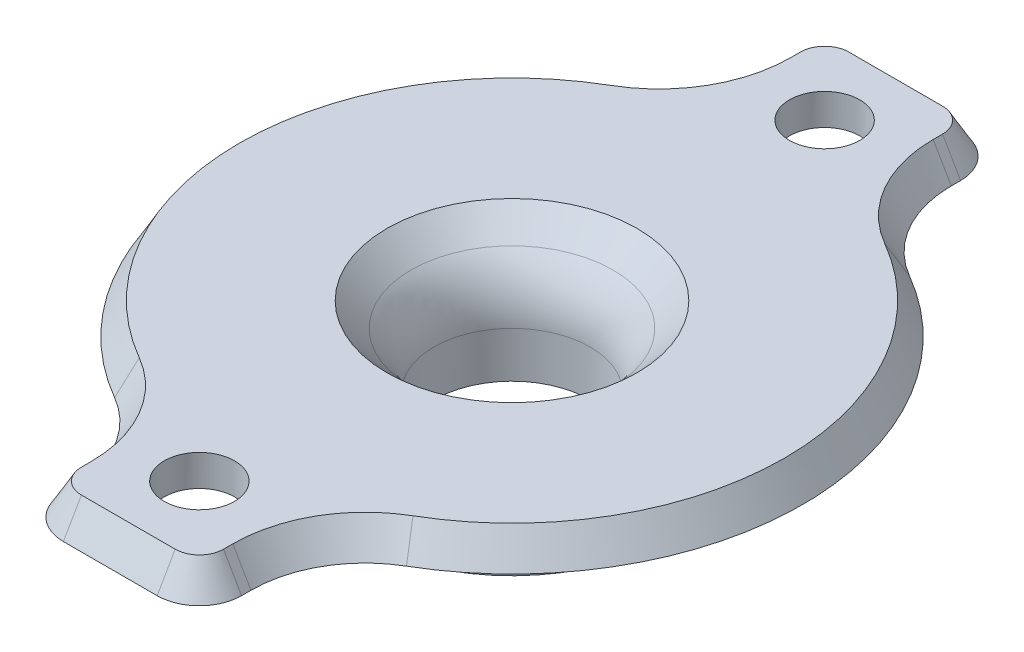
SolidWorks part; units mm, degrees
note: The reader was unsure of these and kept them because the rebuilt part matched: shared geometry of "Sketch2<3>".
ref_plane "Front Plane" through (0, 0, 0) normal (0, 0, 1) x (1, 0, 0)
ref_plane "Top Plane" through (0, 0, 0) normal (0, 1, 0) x (1, 0, 0)
ref_plane "Right Plane" through (0, 0, 0) normal (1, 0, 0) x (0, 0, -1)
sketch "Sketch1" plane through (0, 0, 0) normal (0, 0, 1) x (1, 0, 0)
  line L0 (-5, 0) -> (-5, 2)
  line L1 (55, 0) -> (-55, 0) construction
  line L2 (0, -55) -> (0, 55) construction
  line L3 (-5, 2) -> (-18.6, 2)
  line L4 (-18.6, 2) -> (-18.6, 0)
  line L5 (-18.6, 0) -> (-10.25, 0)
  line L6 (-10.25, 0) -> (-10.25, -6)
  line L7 (-10.25, -6) -> (-5, -6)
  line L8 (-5, -6) -> (-5, 0)
  line L9 (0, 9.8586) -> (0, -23.5452) construction
  dimension "D1" = 5
  dimension "D2" = 6
  dimension "D3" = 10.25
  dimension "D4" = 2
  dimension "D6" = 18.6
revolve "Revolve1" add sketch "Sketch1" angle 360 about L9
sketch "Sketch2" plane through (0, 2, 0) normal (0, 1, 0) x (1, 0, 0)
  line L0 (0, -55) -> (0, 55) construction
  line L1 (-55, 0) -> (55, 0) construction
  line L2 (-5.7, 17.7051) -> (-5.7, 25.7)
  line L3 (-5.7, 25.7) -> (0.0054, 25.7)
  line L4 (-5.7, 17.7051) -> (0, 17.75)
  line L5 (5.7, 25.7) -> (-0.0054, 25.7)
  line L6 (5.7, 17.7051) -> (5.7, 25.7)
  line L7 (5.7, 17.7051) -> (0, 17.75)
  line L8 (5.7, -17.7051) -> (0, -17.75)
  line L9 (5.7, -17.7051) -> (5.7, -25.7)
  line L10 (5.7, -25.7) -> (-0.0054, -25.7)
  line L11 (-5.7, -17.7051) -> (0, -17.75)
  line L12 (-5.7, -25.7) -> (0.0054, -25.7)
  line L13 (-5.7, -17.7051) -> (-5.7, -25.7)
  circle A0 centre (0, 20) radius 2.25
  circle A1 centre (0, 0) radius 18.6 construction
  circle A2 centre (0, -20) radius 2.25
  circle M4 centre (0, 0) radius 18.6
  dimension "D1" = 4.5
  dimension "D2" = 20
  dimension "D3" = 5.7
  dimension "D4" = 5.7
extrude "Boss-Extrude1" add sketch "Sketch2" against normal up to surface (2 mm away) contours A0 L6 L5 L3 L2 M4 | A2 L13 L12 L10 L9 M4 up to face at (0, 0, 10.25)
extrude "Cut-Extrude1" cut sketch "Sketch2<3>" against normal up to surface (2 mm away) contours A0 M4 | A2 M4 up to face at (0, 0, 0)
sketch "Sketch2<3>" plane through (0, 2, 0) normal (0, 1, 0) x (1, 0, 0) same geometry as "Sketch2"
fillet "Fillet1" radius 7.3 4 edges at (5.7, 1, -17.7051) (-5.7, 1, -17.7051) (-5.7, 1, 17.7051) (5.7, 1, 17.7051)
fillet "Fillet2" radius 2.7 4 edges at (-5.7, 1, -25.7) (5.7, 1, -25.7) (-5.7, 1, 25.7) (5.7, 1, 25.7)
chamfer "Chamfer1" distance 2 angle 30 16 edges at (0, 2, 25.7) (5.7, 2, 22.7006) (-5.7, 2, 22.7006) (6.6739, 2, 18.7582) (-6.6739, 2, 18.7582) (18.6, 2, 0) (-18.6, 2, 0) (6.6739, 2, -18.7582) (-6.6739, 2, -18.7582) (5.7, 2, -22.7006) (-5.7, 2, -22.7006) (0, 2, -25.7) (4.9092, 2, 24.9092) (-4.9092, 2, 24.9092) (4.9092, 2, -24.9092) (-4.9092, 2, -24.9092) first distance on face at (0, 1, 25.7) first distance on face at (5.7, 1, 22.7006) first distance on face at (-5.7, 1, 22.7006) first distance on face at (7.096, 1, 19.0012) first distance on face at (-7.096, 1, 19.0012) first distance on face at (13.968, 1, 0) first distance on face at (-13.968, 1, 0) first distance on face at (7.096, 1, -19.0012) first distance on face at (-7.096, 1, -19.0012) first distance on face at (5.7, 1, -22.7006) first distance on face at (-5.7, 1, -22.7006) first distance on face at (0, 1, -25.7) first distance on face at (4.6296, 1, 24.6296) first distance on face at (-4.6296, 1, 24.6296) first distance on face at (4.6296, 1, -24.6296) first distance on face at (-4.6296, 1, -24.6296)
chamfer "Chamfer2" distance 3 1 edges at (0, 2, 5)
fillet "Fillet3" radius 5 1 edges at (0, -1, 5)
chamfer "Chamfer3" distance 2 angle 45 1 edges at (0, 0, 10.25)
